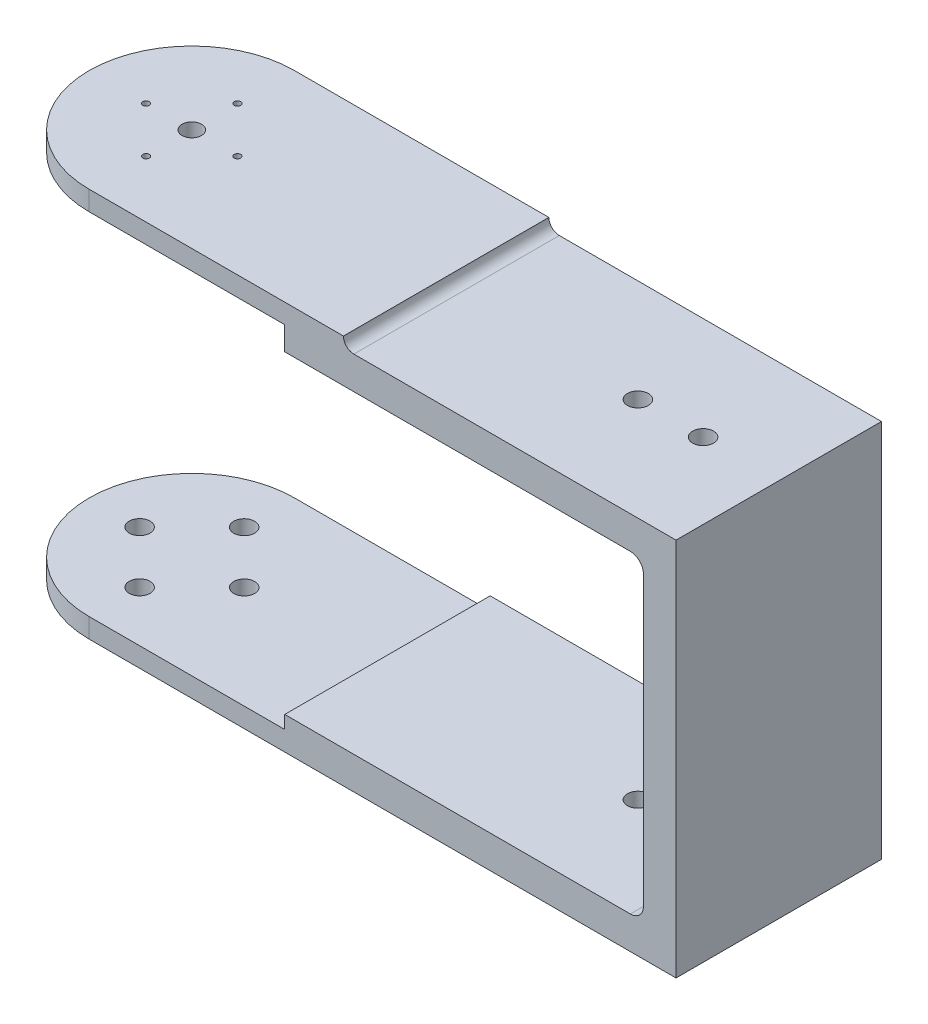
SolidWorks part; units mm, degrees
ref_plane "前视基准面" through (0, 0, 0) normal (0, 0, 1) x (1, 0, 0)
ref_plane "上视基准面" through (0, 0, 0) normal (0, 1, 0) x (1, 0, 0)
ref_plane "右视基准面" through (0, 0, 0) normal (1, 0, 0) x (0, 0, -1)
sketch "草图1" plane through (0, 0, 0) normal (0, 1, 0) x (1, 0, 0)
  line L0 (0, -15.75) -> (90, -15.75)
  line L1 (90, -15.75) -> (90, 15.75)
  line L2 (90, 15.75) -> (0, 15.75)
  arc A0 (0, 15.75) -> (0, -15.75) centre (0, 0) ccw
  dimension "D1" = 31.5
  dimension "D2" = 90
  dimension "D3" = 90
extrude "凸台-拉伸1" add sketch "草图1" along normal blind 3
sketch "草图3" plane through (0, 0, 0) normal (0, -1, 0) x (1, 0, 0)
  line L0 (0, 15.75) -> (90, 15.75) construction
  line L1 (30, 15.75) -> (90, 15.75)
  line L2 (30, 15.75) -> (30, -15.75)
  line L3 (30, -15.75) -> (90, -15.75)
  line L4 (90, 15.75) -> (90, -15.75)
  dimension "D1" = 60
extrude "凸台-拉伸2" add sketch "草图3" along normal blind 2
sketch "草图4" plane through (0, 0, 0) normal (0, -1, 0) x (1, 0, 0)
  circle A4 centre (0, 0) radius 7 construction
  circle A5 centre (0, 7) radius 0.5
  circle A6 centre (7, 0) radius 0.5
  circle A7 centre (0, -7) radius 0.5
  circle A8 centre (-7, 0) radius 0.5
  dimension "D1" = 1
  dimension "D2" = 1
  dimension "D3" = 1
  dimension "D4" = 1
  dimension "D5" = 14
extrude "切除-拉伸1" cut sketch "草图4" against normal blind 10
sketch "草图5" plane through (0, 3, 0) normal (0, 1, 0) x (1, 0, 0)
  circle A0 centre (0, 0) radius 1.5
  dimension "D1" = 3
extrude "切除-拉伸2" cut sketch "草图5" against normal blind 10
sketch "草图6" plane through (0, -2, 0) normal (0, -1, 0) x (1, 0, 0)
  line L0 (30, -15.75) -> (90, -15.75) construction
  line L1 (90, 15.75) -> (85, 15.75)
  line L2 (90, 15.75) -> (90, -15.75)
  line L3 (90, -15.75) -> (85, -15.75)
  line L4 (85, 15.75) -> (85, -15.75)
  dimension "D1" = 5
extrude "凸台-拉伸3" add sketch "草图6" along normal blind 48.15
sketch "草图7" plane through (0, -50.15, 0) normal (0, -1, 0) x (1, 0, 0)
  line L1 (90, 15.75) -> (0, 15.75)
  line L2 (90, 15.75) -> (90, -15.75)
  line L3 (90, -15.75) -> (0, -15.75)
  arc A0 (0, 15.75) -> (0, -15.75) centre (0, 0) ccw
  circle A1 centre (8.0339, 0) radius 1.6
  circle A2 centre (0, 8) radius 1.6
  circle A3 centre (0.0339, -7.9999) radius 1.6
  circle A4 centre (-8, 0) radius 1.6
  dimension "D1" = 3.2
  dimension "D2" = 3.2
  dimension "D3" = 3.2
  dimension "D4" = 3.2
  dimension "D5" = 15.75
  dimension "D6" = 8
  dimension "D7" = 8
  dimension "D8" = 8
  dimension "D9" = 8
extrude "凸台-拉伸4" add sketch "草图7" along normal blind 5
sketch "草图8" plane through (0, -50.15, 0) normal (0, 1, 0) x (1, 0, 0)
  line L0 (0, -15.75) -> (90, -15.75) construction
  line L1 (0, 15.75) -> (30, 15.75)
  line L3 (0, -15.75) -> (30, -15.75)
  line L4 (30, 15.75) -> (30, -15.75)
  line L6 (0, 15.75) -> (-20, 15.75)
  line L8 (0, -15.75) -> (-20, -15.75)
  line L9 (-20, 15.75) -> (-20, -15.75)
  dimension "D1" = 50
extrude "切除-拉伸3" cut sketch "草图8" against normal blind 2
fillet "圆角1" radius 2 1 edges at (85, -2, 0) type face fillet first side face at (85, -26.075, 0) second side face at (57.5, -2, 0)
fillet "圆角2" radius 2 1 edges at (85, -50.15, 0) type face fillet first side face at (85, -27.075, 0) second side face at (57.5, -50.15, 0)
sketch "草图10" plane through (0, 0, 0) normal (0, -1, 0) x (1, 0, 0)
  line L3 (30, -15.75) -> (30, 15.75)
  line L4 (30, 15.75) -> (0, 15.75)
  line L5 (0, -15.75) -> (30, -15.75)
  line L6 (30, -15.75) -> (30, 15.75)
  line L7 (30, 15.75) -> (0, 15.75)
  line L8 (0, -15.75) -> (30, -15.75)
  arc A1 (0, 15.75) -> (0, -15.75) centre (0, 0) ccw
  arc A2 (0, 15.75) -> (0, -15.75) centre (0, 0) ccw
  dimension "D1" = 0
extrude "切除-拉伸5" cut sketch "草图10" against normal blind 1.6
sketch "草图11" plane through (0, 1.6, 0) normal (0, -1, 0) x (1, 0, 0)
  line L3 (0, -15.75) -> (30, -15.75)
  line L4 (30, -15.75) -> (30, 15.75)
  line L5 (30, 15.75) -> (0, 15.75)
  line L6 (0, -15.75) -> (30, -15.75)
  line L7 (30, -15.75) -> (30, 15.75)
  line L8 (30, 15.75) -> (0, 15.75)
  circle A0 centre (0, -7) radius 0.5 construction
  arc A1 (0, 15.75) -> (0, -15.75) centre (0, 0) ccw
  arc A2 (0, 15.75) -> (0, -15.75) centre (0, 0) ccw
  circle A3 centre (-7, 0) radius 0.5 construction
  circle A4 centre (0, 0) radius 1.5 construction
  circle A5 centre (0, 7) radius 0.5 construction
  circle A6 centre (7, 0) radius 0.5 construction
  circle A7 centre (0, -7) radius 0.5
  circle A8 centre (-7, 0) radius 0.5
  circle A9 centre (0, 0) radius 1.5
  circle A10 centre (0, 7) radius 0.5
  circle A11 centre (7, 0) radius 0.5
  dimension "D1" = 0
extrude "凸台-拉伸5" add sketch "草图11" against normal blind 3
sketch "草图12" plane through (30, 0, 0) normal (1, 0, 0) x (0, 0, -1)
  line L1 (-15.75, 4.6) -> (15.75, 4.6)
  line L2 (-15.75, 4.6) -> (-15.75, 3)
  line L3 (-15.75, 3) -> (15.75, 3)
  line L4 (15.75, 4.6) -> (15.75, 3)
extrude "凸台-拉伸6" add sketch "草图12" along normal blind 9
fillet "圆角4" radius 1.6 1 edges at (39, 3, 0) type face fillet first side face at (39, 3.8, 0) second side face at (64.5, 3, 0)
sketch "草图13" plane through (0, 1.6, 0) normal (0, -1, 0) x (1, 0, 0)
  circle A0 centre (0, 0) radius 10
  circle A1 centre (0, 0) radius 1.75
  circle A2 centre (7, 0) radius 0.5
  circle A3 centre (0, -7) radius 0.5
  circle A4 centre (-7, 0) radius 0.5
  circle A5 centre (0, 7) radius 0.5
  dimension "D1" = 20
  dimension "D2" = 3.5
extrude "凸台-拉伸7" add sketch "草图13" along normal blind 1.6
sketch "草图14" plane through (0, -55.15, 0) normal (0, -1, 0) x (1, 0, 0)
  line L1 (0, -15.75) -> (90, -15.75) construction
  line L2 (90, -15.75) -> (90, 15.75) construction
  circle A0 centre (68.4, 0) radius 1.6
  circle A1 centre (78.4, 0) radius 1.6
  point P8 (0, 0)
  dimension "D1" = 3.2
  dimension "D2" = 21.6
  dimension "D4" = 10
  dimension "D3" = 15.75
extrude "切除-拉伸6" cut sketch "草图14" against normal blind 67.6
